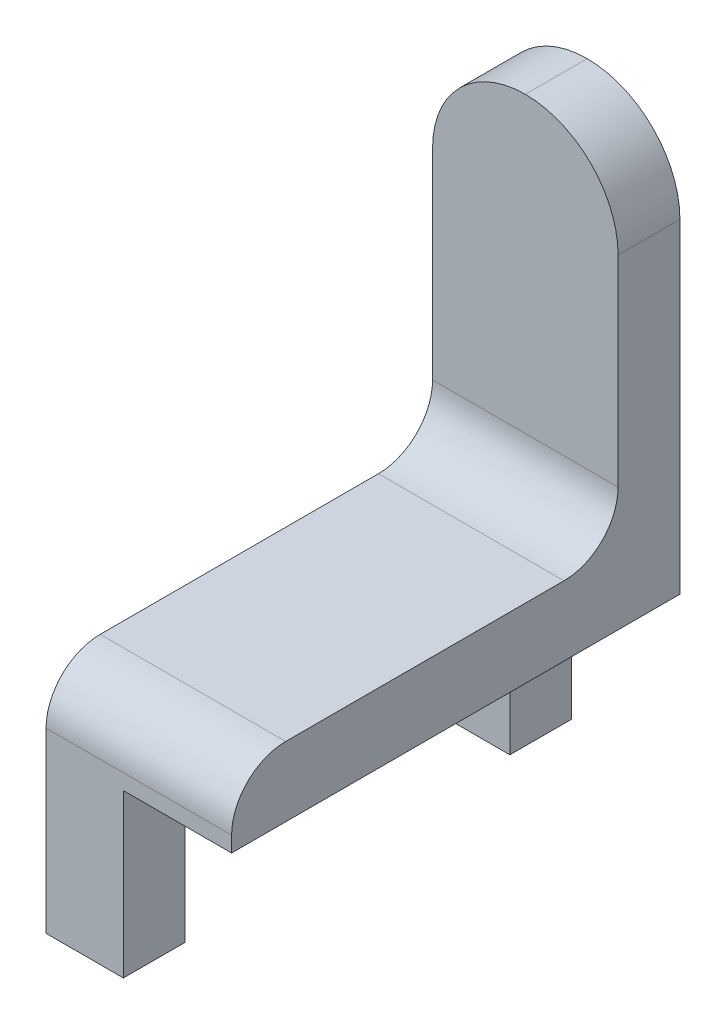
SolidWorks part; units mm, degrees
ref_plane "Front Plane" through (0, 0, 0) normal (0, 0, 1) x (1, 0, 0)
ref_plane "Top Plane" through (0, 0, 0) normal (0, 1, 0) x (1, 0, 0)
ref_plane "Right Plane" through (0, 0, 0) normal (1, 0, 0) x (0, 0, -1)
sketch "Sketch2" plane through (0, -0.0002, -27.9978) normal (0, 0, -1) x (1, 0, 0)
  line L1 (45.1952, -27.127) -> (69.1952, -27.127)
  line L2 (45.1952, -27.127) -> (45.1952, 47.873)
  line L3 (45.1952, 47.873) -> (69.1952, 47.873)
  line L4 (69.1952, -27.127) -> (69.1952, 47.873)
  dimension "D4" = 75
extrude "Boss-Extrude1" add sketch "Sketch2" along normal blind 8
fillet "Fillet1" radius 12 2 edges at (45.1952, 27.1268, -31.9981) (69.1952, 27.1268, -31.9981)
sketch "Sketch3" plane through (0, -0.0002, -27.9978) normal (0, 0, 1) x (1, 0, 0)
  line L0 (69.1952, 15.127) -> (69.1952, -47.873) construction
  line L1 (45.1952, -47.873) -> (69.1952, -47.873)
  line L2 (45.1952, -47.873) -> (45.1952, -17.873)
  line L3 (45.1952, -17.873) -> (69.1952, -17.873)
  line L4 (69.1952, -47.873) -> (69.1952, -17.873)
  dimension "D1" = 30
extrude "Boss-Extrude2" add sketch "Sketch3" along normal blind 50
sketch "Sketch4" plane through (69.1952, 0, 0) normal (1, 0, 0) x (0, 0, -1)
  line L2 (27.9977, -54.1007) -> (27.9977, -26.8732)
  line L3 (27.9977, -26.8732) -> (-14.0023, -26.8732)
  line L4 (-14.0023, -54.1007) -> (-14.0023, -26.8732)
  line L5 (-22.0023, -17.8728) -> (35.9977, -17.8728) construction
  line L6 (35.998, 15.1267) -> (35.9975, -47.8733) construction
  line L7 (6.9977, -17.8728) -> (6.9977, -54.1007) construction
  line L8 (27.9977, -54.1007) -> (-14.0023, -54.1007)
  dimension "D1" = 21
  dimension "D2" = 42
extrude "Cut-Extrude1" cut sketch "Sketch4" against normal up to surface (24 mm away) up to face at (45.1952, -16.8731, -13.9977)
fillet "Fillet2" radius 7 2 edges at (57.1952, -17.8728, 22.0023) (57.1952, -17.8732, -27.9977)
sketch "Sketch5" plane through (69.1952, 0, 0) normal (1, 0, 0) x (0, 0, -1)
  line L10 (-22.0025, -47.8728) -> (-22.0024, -24.8728) construction
  line L11 (35.998, 15.1267) -> (35.9975, -47.8733) construction
  line L20 (20.9977, -17.8732) -> (-15.0023, -17.8729)
  line L21 (-22.0024, -24.8728) -> (-22.0025, -47.8728)
  line L22 (-22.0025, -47.8728) -> (-14.0023, -47.8729)
  line L23 (-14.0023, -47.8729) -> (-14.0023, -26.8732)
  line L24 (-14.0023, -26.8732) -> (27.9977, -26.8732)
  line L25 (27.9977, -26.8732) -> (27.9977, -47.8732)
  line L26 (27.9977, -47.8732) -> (35.9975, -47.8733)
  line L27 (35.9975, -47.8733) -> (35.998, 15.1267)
  line L28 (35.998, 15.1267) -> (27.998, 15.1268)
  line L29 (27.998, 15.1268) -> (27.9978, -10.8732)
  line L31 (-22.0024, -26.8732) -> (-22.0025, -47.8728)
  line L32 (-22.0025, -47.8728) -> (35.9975, -47.8733)
  line L34 (-22.0024, -26.8732) -> (35.9976, -26.8732)
  line L37 (35.9975, -47.8733) -> (35.9976, -26.8732)
  arc A2 (-15.0023, -17.8729) -> (-22.0024, -24.8728) centre (-15.0024, -24.8729) ccw
  arc A3 (20.9977, -17.8732) -> (27.9978, -10.8732) centre (20.9978, -10.8732) ccw
  point P2 (0, 0)
  point P8 (35.479, -47.8733)
  point P9 (-22.0024, -26.8732)
  point P18 (35.9976, -26.8732)
  dimension "D1" = 0
extrude "Cut-Extrude3" cut sketch "Sketch5" against normal blind 14
